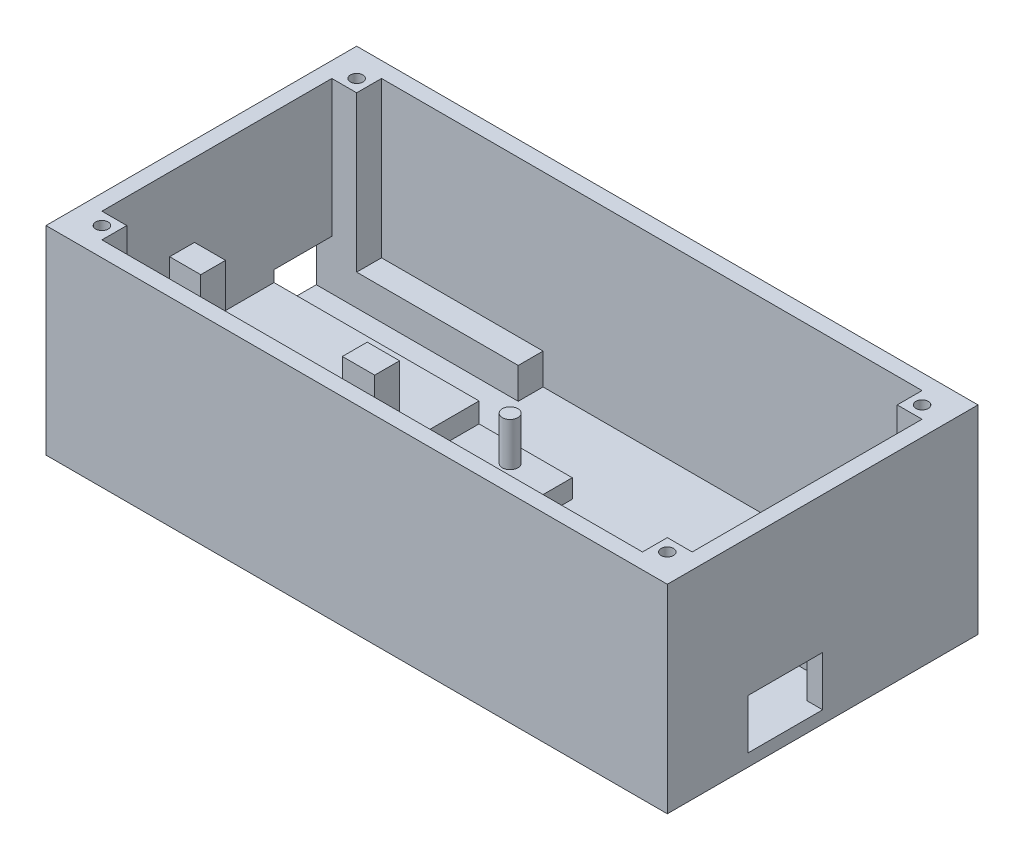
SolidWorks part; units mm, degrees
ref_plane "Front Plane" through (0, 0, 0) normal (0, 0, 1) x (1, 0, 0)
ref_plane "Top Plane" through (0, 0, 0) normal (0, 1, 0) x (1, 0, 0)
ref_plane "Right Plane" through (0, 0, 0) normal (1, 0, 0) x (0, 0, -1)
sketch "Sketch1" plane through (0, 0, 0) normal (0, 1, 0) x (1, 0, 0)
  line L1 (0, 0) -> (100, 0)
  line L2 (0, 0) -> (0, 50)
  line L3 (0, 50) -> (100, 50)
  line L4 (100, 0) -> (100, 50)
  dimension "D1" = 100
  dimension "D2" = 50
extrude "Boss-Extrude1" add sketch "Sketch1" along normal blind 2
sketch "Sketch3" plane through (0, 2, 0) normal (0, 1, 0) x (1, 0, 0)
  line L1 (0, 50) -> (100, 50)
  line L2 (0, 50) -> (0, 0)
  line L3 (0, 0) -> (100, 0)
  line L4 (100, 50) -> (100, 0)
  line L5 (6.5, 47.5) -> (93.5, 47.5)
  line L6 (2.5, 43.5) -> (2.5, 6.5)
  line L7 (6.5, 2.5) -> (93.5, 2.5)
  line L8 (97.5, 43.5) -> (97.5, 6.5)
  line L11 (2.5, 43.5) -> (6.5, 43.5)
  line L12 (6.5, 47.5) -> (6.5, 43.5)
  line L14 (97.5, 43.5) -> (93.5, 43.5)
  line L15 (93.5, 47.5) -> (93.5, 43.5)
  line L16 (97.5, 6.5) -> (93.5, 6.5)
  line L17 (93.5, 2.5) -> (93.5, 6.5)
  line L18 (6.5, 2.5) -> (6.5, 6.5)
  line L19 (2.5, 6.5) -> (6.5, 6.5)
  line L20 (6.5, 47.5) -> (2.5, 43.5) construction
  circle A0 centre (4.5, 45.5) radius 1
  circle A1 centre (95.5, 45.5) radius 1
  circle A2 centre (95.5, 4.5) radius 1
  circle A3 centre (4.5, 4.5) radius 1
  dimension "D7" = 2
  dimension "D8" = 2
  dimension "D1" = 2.5
  dimension "D2" = 2.5
  dimension "D3" = 2.5
  dimension "D4" = 2.5
  dimension "D5" = 4
  dimension "D6" = 4
  dimension "D9" = 2
extrude "Boss-Extrude2" add sketch "Sketch3" along normal blind 30
sketch "Sketch4" plane through (0, 2, 0) normal (0, 1, 0) x (1, 0, 0)
  line L2 (2.5, 43.5) -> (2.5, 6.5) construction
  line L3 (2.5, 34.2) -> (35.5, 34.2)
  line L4 (2.5, 34.2) -> (2.5, 6.5)
  line L5 (6.5, 2.5) -> (35.5, 2.5)
  line L6 (35.5, 34.2) -> (35.5, 2.5)
  line L7 (6.5, 2.5) -> (93.5, 2.5) construction
  line L8 (2.5, 6.5) -> (6.5, 6.5)
  line L9 (6.5, 6.5) -> (6.5, 2.5)
  dimension "D1" = 27.7
  dimension "D4" = 33
extrude "Boss-Extrude3" add sketch "Sketch4" along normal blind 6.2
sketch "Sketch5" plane through (0, 2, 0) normal (0, 1, 0) x (1, 0, 0)
  line L0 (0, 0) -> (0, 29.9) construction
  line L1 (0, 50) -> (0, 0) construction
  point P5 (0, 26.7)
  point P6 (0, 15.9)
  dimension "D1" = 29.9
  dimension "D2" = 26.7
  dimension "D3" = 15.9
sketch "Sketch6" plane through (0, 8.2, 0) normal (0, 1, 0) x (1, 0, 0)
  line L0 (2.5, 43.5) -> (2.5, 6.5) construction
  line L1 (2.5, 21.4) -> (7.5, 21.4)
  line L2 (2.5, 21.4) -> (2.5, 17.4)
  line L3 (2.5, 17.4) -> (7.5, 17.4)
  line L4 (7.5, 21.4) -> (7.5, 17.4)
  line L5 (35.5, 2.5) -> (35.5, 34.2) construction
  line L6 (30.3, 21.4) -> (35.5, 21.4)
  line L7 (30.3, 21.4) -> (30.3, 17.4)
  line L8 (30.3, 17.4) -> (35.5, 17.4)
  line L9 (35.5, 21.4) -> (35.5, 17.4)
  dimension "D1" = 5
  dimension "D2" = 4
  dimension "D3" = 22.8
  dimension "D4" = 21.4
extrude "Boss-Extrude4" add sketch "Sketch6" along normal blind 12
sketch "Sketch7" plane through (2.5, 0, 0) normal (1, 0, 0) x (0, 0, -1)
  line L0 (43.5, 32) -> (43.5, 2) construction
  line L1 (34.2, 2) -> (43.5, 2)
  line L2 (34.2, 2) -> (34.2, 10)
  line L3 (34.2, 10) -> (43.5, 10)
  line L4 (43.5, 2) -> (43.5, 10)
  dimension "D2" = 8
extrude "Cut-Extrude1" cut sketch "Sketch7" against normal blind 15
sketch "Sketch8" plane through (97.5, 0, 0) normal (-1, 0, 0) x (0, 0, 1)
  line L0 (-6.5, 2) -> (-43.5, 2) construction
  line L1 (-25, 2) -> (-13, 2)
  line L2 (-25, 2) -> (-25, 10)
  line L3 (-25, 10) -> (-13, 10)
  line L4 (-13, 2) -> (-13, 10)
  line L5 (-6.5, 32) -> (-6.5, 2) construction
  point P8 (-13, 6)
  dimension "D1" = 6.5
  dimension "D2" = 12
  dimension "D3" = 8
sketch "Sketch9" plane through (0, 2, 0) normal (0, 1, 0) x (1, 0, 0)
  line L0 (93.5, 47.5) -> (6.5, 47.5) construction
  line L1 (2.5, 43.5) -> (32.5, 43.5)
  line L2 (2.5, 43.5) -> (2.5, 47.5)
  line L3 (2.5, 47.5) -> (32.5, 47.5)
  line L4 (32.5, 43.5) -> (32.5, 47.5)
  line L5 (6.5, 43.5) -> (2.5, 43.5) construction
  line L6 (78.5, 43.5) -> (93.5, 43.5)
  line L7 (78.5, 43.5) -> (78.5, 47.5)
  line L8 (78.5, 47.5) -> (93.5, 47.5)
  line L9 (93.5, 43.5) -> (93.5, 47.5)
  dimension "D1" = 30
  dimension "D3" = 15
extrude "Boss-Extrude5" add sketch "Sketch9" along normal blind 5
sketch "Sketch12" plane through (0, 2, 0) normal (0, 1, 0) x (1, 0, 0)
  line L0 (35.5, 34.2) -> (97.5, 34.2) construction
  line L1 (97.5, 6.5) -> (97.5, 43.5) construction
  circle A0 centre (90, 7.7) radius 1.25
  circle A1 centre (43.5, 7.7) radius 1.25
  circle A2 centre (43.5, 31.2) radius 1.25
  circle A3 centre (90, 31.2) radius 1.25
  dimension "D3" = 2.5
  dimension "D6" = 2
  dimension "D7" = 2
extrude "Boss-Extrude6" add sketch "Sketch12" along normal blind 10
extrude "Cut-Extrude2" cut sketch "Sketch8" against normal blind 10
sketch "Sketch13" plane through (0, 2, 0) normal (0, 1, 0) x (1, 0, 0)
  line L0 (97.5, 25) -> (97.5, 43.5) construction
  line L1 (77.5, 34.2) -> (97.5, 34.2)
  line L2 (77.5, 34.2) -> (77.5, 29.2)
  line L3 (77.5, 29.2) -> (97.5, 29.2)
  line L4 (97.5, 34.2) -> (97.5, 29.2)
  line L5 (35.5, 34.2) -> (2.5, 34.2) construction
  line L7 (35.5, 34.2) -> (50.5, 34.2)
  line L8 (35.5, 34.2) -> (35.5, 29.2)
  line L9 (35.5, 29.2) -> (50.5, 29.2)
  line L10 (50.5, 34.2) -> (50.5, 29.2)
  dimension "D1" = 20
  dimension "D2" = 5
  dimension "D3" = 15
extrude "Boss-Extrude7" add sketch "Sketch13" along normal blind 3
